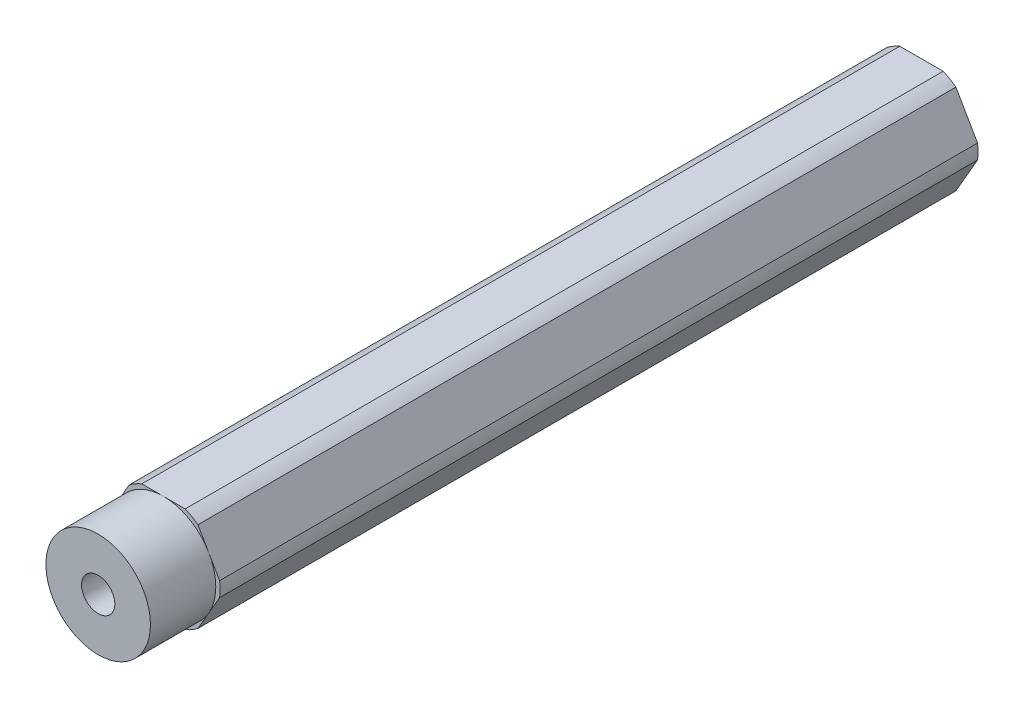
SolidWorks part; units mm, degrees
ref_plane "Front Plane" through (0, 0, 0) normal (0, 0, 1) x (1, 0, 0)
ref_plane "Top Plane" through (0, 0, 0) normal (0, 1, 0) x (1, 0, 0)
ref_plane "Right Plane" through (0, 0, 0) normal (1, 0, 0) x (0, 0, -1)
sketch "Sketch1" plane through (0, 0, 0) normal (0, 0, 1) x (1, 0, 0)
  line L1 (3.6662, 6.35) -> (-3.6662, 6.35)
  line L2 (-3.6662, 6.35) -> (-7.3323, 0)
  line L3 (-7.3323, 0) -> (-3.6662, -6.35)
  line L4 (-3.6662, -6.35) -> (3.6662, -6.35)
  line L5 (3.6662, -6.35) -> (7.3323, 0)
  line L6 (7.3323, 0) -> (3.6662, 6.35)
  circle A0 centre (0, 0) radius 6.35 construction
  circle A1 centre (0, 0) radius 6.875
  circle A2 centre (0, 0) radius 2.0193
  point P10 (0, 6.35)
  dimension "D1" = 13.75
  dimension "D2" = 12.7
  dimension "D3" = 4.0386
extrude "Boss-Extrude1" add sketch "Sketch1" along normal mid plane 100.0125 contours L6 A1 L1 L2 L3 L4 L5 region at (3.3439, 5.7918, 0)
sketch "Sketch2" plane through (0, 0, 50.0062) normal (0, 0, 1) x (1, 0, 0)
  circle A0 centre (0, 0) radius 6.35
  dimension "D1" = 12.7
extrude "Cut-Extrude2" cut sketch "Sketch2" against normal blind 7.9375 flip side to cut
equation "\"D1@Sketch1\"=13.75mm"
